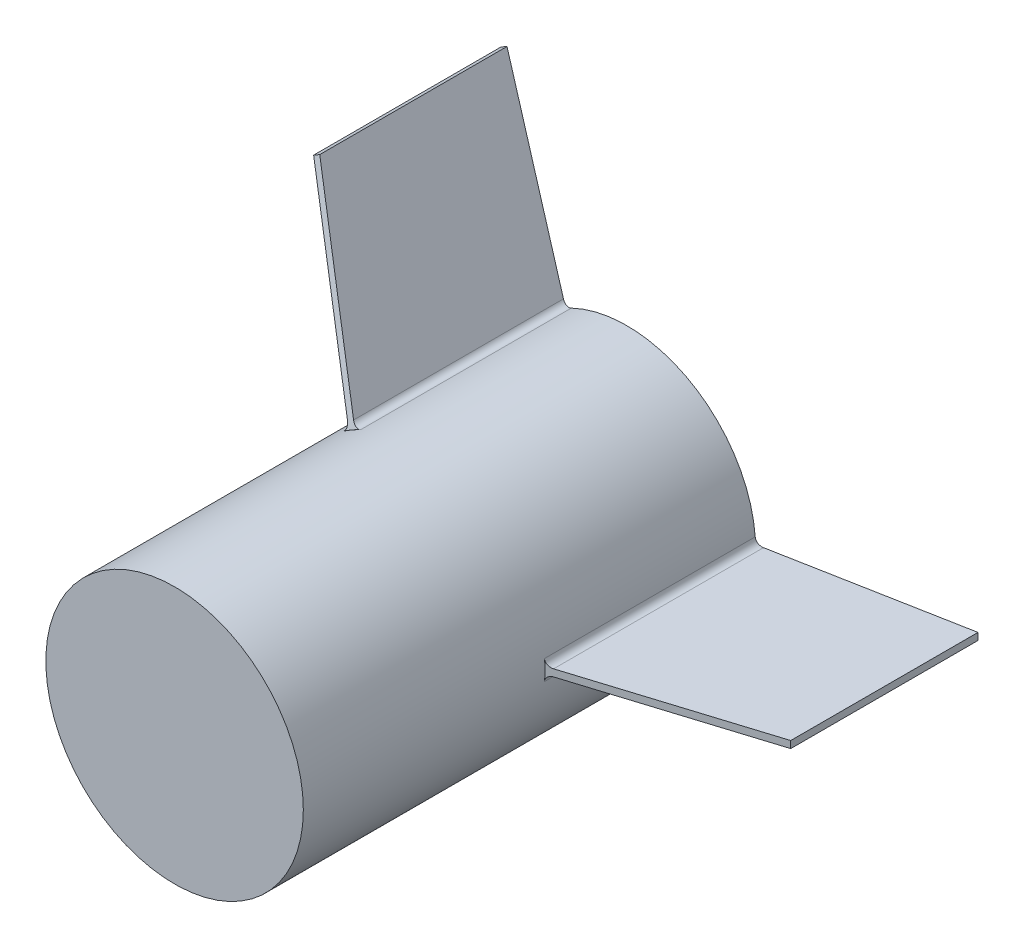
SolidWorks part; units mm, degrees
ref_plane "前视基准面" through (0, 0, 0) normal (0, 0, 1) x (1, 0, 0)
ref_plane "上视基准面" through (0, 0, 0) normal (0, 1, 0) x (1, 0, 0)
ref_plane "右视基准面" through (0, 0, 0) normal (1, 0, 0) x (0, 0, -1)
other "Configuration Table"
sketch "草图1" plane through (0, 0, 0) normal (0, 0, 1) x (1, 0, 0)
  circle A1 centre (0, 0) radius 55
  dimension "D1" = 110
extrude "凸台-拉伸1" add sketch "草图1" along normal blind 190
sketch "草图2" plane through (0, 0, 190) normal (0, 0, 1) x (1, 0, 0)
  circle A0 centre (0, 0) radius 51.8
  dimension "D1" = 103.6
extrude "切除-拉伸1" cut sketch "草图2" against normal blind 186.8
sketch "草图3" plane through (0, 0, 0) normal (0, 0, -1) x (-1, 0, 0)
  circle A0 centre (0, 0) radius 15
  dimension "D1" = 30
extrude "切除-拉伸2" cut sketch "草图3" against normal blind 10
sketch "草图4" plane through (0, 0, 3.2) normal (0, 0, 1) x (1, 0, 0)
  circle A0 centre (0, 0) radius 15
  circle A1 centre (0, 0) radius 18.2
  dimension "D1" = 36.4
extrude "凸台-拉伸2" add sketch "草图4" along normal blind 188
sketch "草图5" plane through (0, 0, 190) normal (0, 0, 1) x (1, 0, 0)
  circle A0 centre (0, 0) radius 55
extrude "凸台-拉伸5" add sketch "草图5" along normal blind 3.2
sketch "草图6" plane through (0, 0, 193.2) normal (0, 0, 1) x (1, 0, 0)
  line L0 (0, 0) -> (-55, 0)
  line L1 (0, 0) -> (27.5, 47.6314)
  line L2 (0, 0) -> (27.5, -47.6314)
  circle A0 centre (0, 0) radius 55 construction
  point P10 (0, 0)
  dimension "D1" = 3
ref_plane "基准面1" through (0, 0, 0) normal (0, 1, 0) x (-1, 0, 0)
sketch "草图8" plane through (0, 0, 0) normal (0, 1, 0) x (-1, 0, 0)
  line L0 (-55, 90) -> (-135, 65)
  line L1 (-55, 193.2) -> (-55, 0) construction
  line L2 (-135, 65) -> (-135, -15)
  line L3 (-135, -15) -> (-55, 0)
  line L5 (-55, 90) -> (-53, 90)
  line L6 (-53, 90) -> (-53, 0)
  line L7 (-55, 0) -> (55, 0) construction
  line L8 (-53, 0) -> (-55, 0)
  dimension "D1" = 65
  dimension "D2" = 25
  dimension "D3" = 80
  dimension "D4" = 2
  dimension "D5" = 80
extrude "凸台-拉伸6" add sketch "草图8" along normal mid plane 3
pattern_circular "阵列(圆周)1" count 3 over 360 about axis through (0, 0, 190) along (0, 0, -1) of "凸台-拉伸6"
fillet "圆角1" radius 3 6 edges at (-28.7888, -46.8637, 45) (-26.1907, -48.3637, 45) (54.9795, -1.5, 45) (54.9795, 1.5, 45) (-26.1907, 48.3637, 45) (-28.7888, 46.8637, 45)
equation "\"3。2\"=1"
